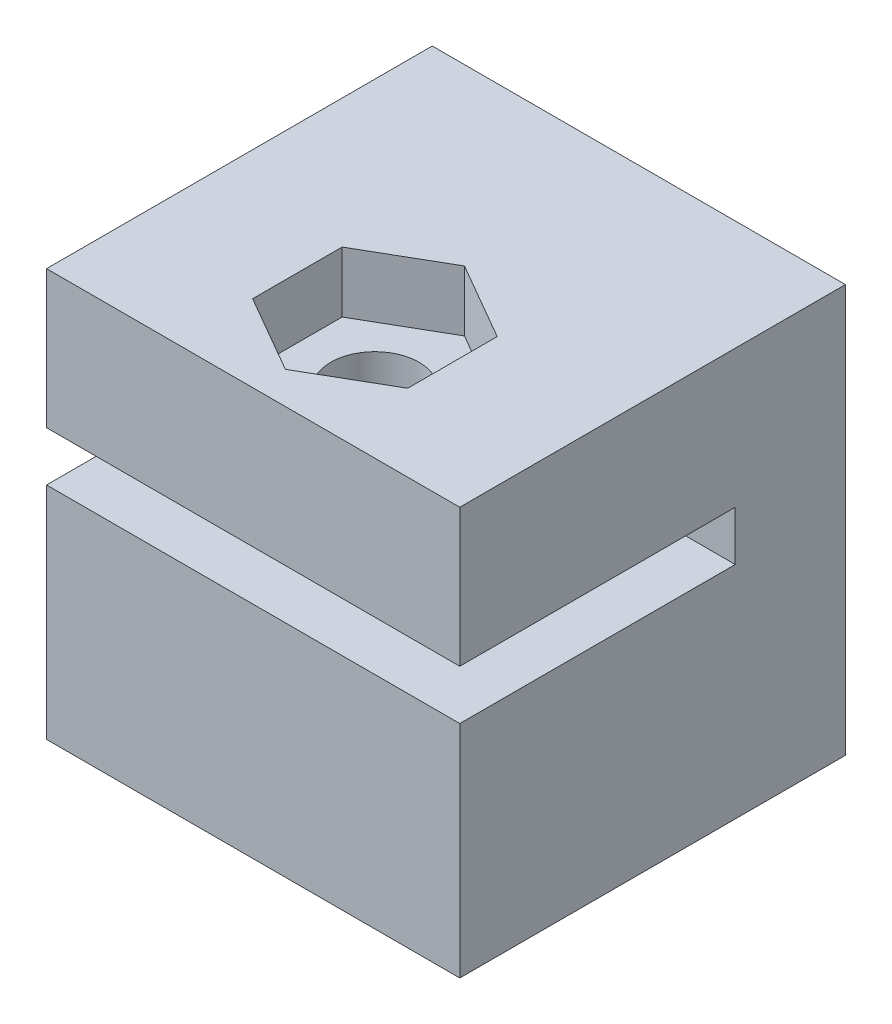
SolidWorks part; units mm, degrees
ref_plane "Front Plane" through (0, 0, 0) normal (0, 0, 1) x (1, 0, 0)
ref_plane "Top Plane" through (0, 0, 0) normal (0, 1, 0) x (1, 0, 0)
ref_plane "Right Plane" through (0, 0, 0) normal (1, 0, 0) x (0, 0, -1)
sketch "Sketch1" plane through (0, 0, 0) normal (0, 1, 0) x (1, 0, 0)
  line L1 (-7.5, 7) -> (7.5, 7)
  line L2 (-7.5, 7) -> (-7.5, -7)
  line L3 (-7.5, -7) -> (7.5, -7)
  line L4 (7.5, 7) -> (7.5, -7)
  line L5 (-7.5, 7) -> (7.5, -7) construction
  line L6 (-7.5, -7) -> (7.5, 7) construction
  point P0 (0, 0)
  dimension "D1" = 15
  dimension "D2" = 14
extrude "base" add sketch "Sketch1" along normal blind 8
sketch "Sketch3" plane through (0, 8, 0) normal (0, 1, 0) x (1, 0, 0)
  line L0 (-5.9962, -7) -> (5.9962, -7)
  line L1 (-7.5, -7) -> (7.5, -7) construction
  line L3 (-5.9962, -7) -> (5.9962, -7)
  line L4 (-5.9962, -7) -> (-5.9962, 1)
  line L5 (-5.9962, 1) -> (5.9962, 1)
  line L6 (5.9962, -7) -> (5.9962, 1)
  line L7 (-7.5, 7) -> (7.5, 7)
  line L8 (-7.5, 7) -> (-7.5, -7)
  line L9 (-7.5, -7) -> (7.5, -7)
  line L10 (7.5, 7) -> (7.5, -7)
  line L11 (-7.5, 7) -> (7.5, 7)
  line L12 (-7.5, 7) -> (-7.5, 3)
  line L13 (-7.5, 3) -> (7.5, 3)
  line L14 (7.5, 7) -> (7.5, 3)
  point P5 (0, -7)
  line M14 (7.5, 7) -> (-7.5, 7)
  line M15 (-7.5, 7) -> (-7.5, -7)
  dimension "D1" = 8
extrude "spacer" add sketch "Sketch3" along normal blind 1.8 contours L13 L5 L10 M15 M14 region at (0, 8, -5)
sketch "Sketch4" plane through (0, 9.8, 0) normal (0, 1, 0) x (1, 0, 0)
  line L1 (-7.5, 7) -> (7.5, 7)
  line L2 (-7.5, 7) -> (-7.5, -7)
  line L3 (-7.5, -7) -> (7.5, -7)
  line L4 (7.5, 7) -> (7.5, -7)
  dimension "D1" = 14
extrude "top" add sketch "Sketch4" along normal blind 5
sketch "Sketch5" plane through (0, 14.8, 0) normal (0, 1, 0) x (1, 0, 0)
  line L0 (-6.0022, -7) -> (6.0022, -7)
  line L1 (-7.5, -7) -> (7.5, -7) construction
  line L2 (0, 7) -> (0, -2.58)
  line L3 (-6.0022, -7) -> (6.0022, -7)
  line L4 (-6.0022, -7) -> (-6.0022, 3)
  line L5 (-6.0022, 3) -> (6.0022, 3)
  line L6 (6.0022, -7) -> (6.0022, 3)
  line L7 (7.5, 7) -> (-7.5, 7) construction
  circle A1 centre (0, -2.58) radius 1.6
  point P5 (0, -7)
  dimension "D1" = 3.2
  dimension "D3" = 9.58
extrude "bore" cut sketch "Sketch5" against normal through all contours A1
sketch "Sketch6" plane through (0, 14.8, 0) normal (0, 1, 0) x (1, 0, 0)
  line L7 (0, 0.67) -> (-2.8146, -0.955)
  line L8 (-2.8146, -0.955) -> (-2.8146, -4.205)
  line L9 (-2.8146, -4.205) -> (0, -5.83)
  line L10 (0, -5.83) -> (2.8146, -4.205)
  line L11 (2.8146, -4.205) -> (2.8146, -0.955)
  line L12 (2.8146, -0.955) -> (0, 0.67)
  circle A0 centre (0, -2.58) radius 2.8146 construction
  dimension "D1" = 6.5
extrude "nut" cut sketch "Sketch6" against normal blind 2.2 contours L7 L8 L9 L10 L11 L12
